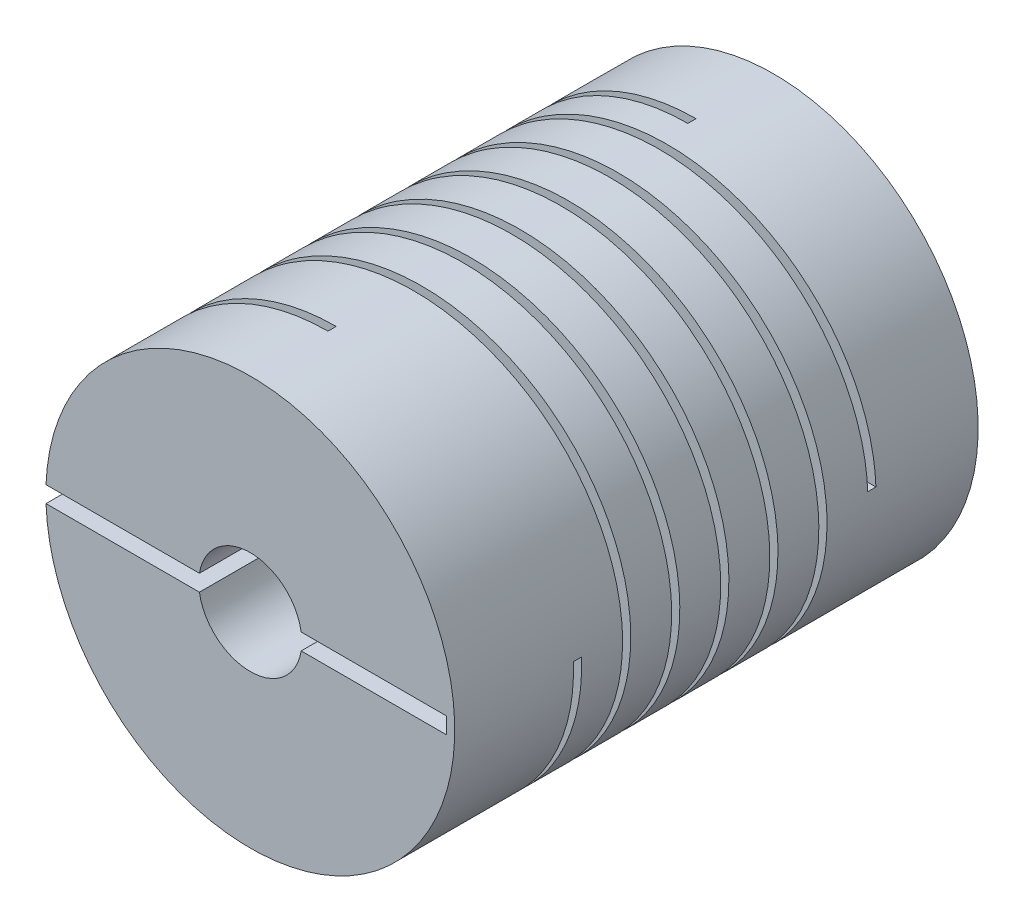
SolidWorks part; units mm, degrees
material "3,3523 (EN-AW 5052)"
ref_plane "Plano frontal" through (0, 0, 0) normal (0, 0, 1) x (1, 0, 0)
ref_plane "Plano superior" through (0, 0, 0) normal (0, 1, 0) x (1, 0, 0)
ref_plane "Plano direito" through (0, 0, 0) normal (1, 0, 0) x (0, 0, -1)
sketch "Esboço1" plane through (0, 0, 0) normal (0, 0, 1) x (1, 0, 0)
  circle A0 centre (0, 0) radius 12.5
  dimension "D1" = 25
extrude "Ressalto-extrusão1" add sketch "Esboço1" along normal blind 32
sketch "Esboço2" plane through (0, 0, 32) normal (0, 0, 1) x (1, 0, 0)
  circle A0 centre (0, 0) radius 3.15
  dimension "D1" = 6.3
extrude "Corte-extrusão1" cut sketch "Esboço2" against normal blind 32
sketch "Esboço3" plane through (0, 0, 0) normal (1, 0, 0) x (0, 0, -1)
  line L0 (-27, 12.5) -> (-27, -12.5) construction
  line L1 (-26.75, 12.5) -> (-26.75, -12.5)
  line L2 (-27.25, 12.5) -> (-27.25, -12.5)
  line L3 (-5, 12.5) -> (-5, -12.5) construction
  line L4 (-4.75, 12.5) -> (-4.75, -12.5)
  line L5 (-5.25, 12.5) -> (-5.25, -12.5)
  line L6 (-32, 12.5) -> (-32, -12.5) construction
  line L7 (0, -12.5) -> (0, 12.5) construction
  arc A0 (-26.75, 12.5) -> (-27.25, 12.5) centre (-27, 12.5) ccw
  arc A1 (-27.25, -12.5) -> (-26.75, -12.5) centre (-27, -12.5) ccw
  arc A2 (-4.75, 12.5) -> (-5.25, 12.5) centre (-5, 12.5) ccw
  arc A3 (-5.25, -12.5) -> (-4.75, -12.5) centre (-5, -12.5) ccw
  point P2 (-27, 0)
  point P7 (-5, 0)
  dimension "D5" = 0.25
  dimension "D6" = 0.25
  dimension "D1" = 5
  dimension "D2" = 5
  dimension "D3" = 25
  dimension "D4" = 25
extrude "Corte-extrusão2" cut sketch "Esboço3" against normal blind 16
ref_plane "Plano1" through (0, 0, 24.5) normal (0, 0, 1) x (1, 0, 0)
sketch "Esboço5" plane through (0, 0, 24.5) normal (0, 0, 1) x (1, 0, 0)
  circle A0 centre (0, 0) radius 12.5
  dimension "D1" = 25
curve "Hélice/Espiral1" pitch 3 height 18 radius 12.5 centre (0, 0, 24.5) axis (0, 0, -1) start towards (1, 0, 0)
sketch "Esboço6" plane through (0, 0, 0) normal (0, 1, 0) x (1, 0, 0)
  line L0 (12.5, -32) -> (12.5, 0) construction
  line L1 (12.5, -6.25) -> (2.5, -6.25)
  line L2 (12.5, -6.25) -> (12.5, -6.75)
  line L3 (12.5, -6.75) -> (2.5, -6.75)
  line L4 (2.5, -6.25) -> (2.5, -6.75)
  spline S0 degree 3 poles (12.5, -24.5) (12.5, -24.4379) (11.8491, -24.3123) (9.0689, -24.125) (4.9081, -23.9375) (0, -23.75) (-4.9081, -23.5625) (-9.0689, -23.375) (-11.8491, -23.1875) (-12.8254, -23) (-11.8491, -22.8125) (-9.0689, -22.625) (-4.9081, -22.4375) (0, -22.25) (4.9081, -22.0625) (9.0689, -21.875) (11.8491, -21.6875) (12.8254, -21.5) (11.8491, -21.3125) (9.0689, -21.125) (4.9081, -20.9375) (0, -20.75) (-4.9081, -20.5625) (-9.0689, -20.375) (-11.8491, -20.1875) (-12.8254, -20) (-11.8491, -19.8125) (-9.0689, -19.625) (-4.9081, -19.4375) (0, -19.25) (4.9081, -19.0625) (9.0689, -18.875) (11.8491, -18.6875) (12.8254, -18.5) (11.8491, -18.3125) (9.0689, -18.125) (4.9081, -17.9375) (0, -17.75) (-4.9081, -17.5625) (-9.0689, -17.375) (-11.8491, -17.1875) (-12.8254, -17) (-11.8491, -16.8125) (-9.0689, -16.625) (-4.9081, -16.4375) (0, -16.25) (4.9081, -16.0625) (9.0689, -15.875) (11.8491, -15.6875) (12.8254, -15.5) (11.8491, -15.3125) (9.0689, -15.125) (4.9081, -14.9375) (0, -14.75) (-4.9081, -14.5625) (-9.0689, -14.375) (-11.8491, -14.1875) (-12.8254, -14) (-11.8491, -13.8125) (-9.0689, -13.625) (-4.9081, -13.4375) (0, -13.25) (4.9081, -13.0625) (9.0689, -12.875) (11.8491, -12.6875) (12.8254, -12.5) (11.8491, -12.3125) (9.0689, -12.125) (4.9081, -11.9375) (0, -11.75) (-4.9081, -11.5625) (-9.0689, -11.375) (-11.8491, -11.1875) (-12.8254, -11) (-11.8491, -10.8125) (-9.0689, -10.625) (-4.9081, -10.4375) (0, -10.25) (4.9081, -10.0625) (9.0689, -9.875) (11.8491, -9.6875) (12.8254, -9.5) (11.8491, -9.3125) (9.0689, -9.125) (4.9081, -8.9375) (0, -8.75) (-4.9081, -8.5625) (-9.0689, -8.375) (-11.8491, -8.1875) (-12.8254, -8) (-11.8491, -7.8125) (-9.0689, -7.625) (-4.9081, -7.4375) (0, -7.25) (4.9081, -7.0625) (9.0689, -6.875) (11.8491, -6.6877) (12.5, -6.5621) (12.5, -6.5) knots 0 0 0 0 0.010417 0.020833 0.03125 0.041667 0.052083 0.0625 0.072917 0.083333 0.09375 0.104167 0.114583 0.125 0.135417 0.145833 0.15625 0.166667 0.177083 0.1875 0.197917 0.208333 0.21875 0.229167 0.239583 0.25 0.260417 0.270833 0.28125 0.291667 0.302083 0.3125 0.322917 0.333333 0.34375 0.354167 0.364583 0.375 0.385417 0.395833 0.40625 0.416667 0.427083 0.4375 0.447917 0.458333 0.46875 0.479167 0.489583 0.5 0.510417 0.520833 0.53125 0.541667 0.552083 0.5625 0.572917 0.583333 0.59375 0.604167 0.614583 0.625 0.635417 0.645833 0.65625 0.666667 0.677083 0.6875 0.697917 0.708333 0.71875 0.729167 0.739583 0.75 0.760417 0.770833 0.78125 0.791667 0.802083 0.8125 0.822917 0.833333 0.84375 0.854167 0.864583 0.875 0.885417 0.895833 0.90625 0.916667 0.927083 0.9375 0.947917 0.958333 0.96875 0.979167 0.989583 1 1 1 1 construction
  point P8 (12.5, -6.5)
  dimension "D1" = 0.5
  dimension "D2" = 10
  dimension "D3" = 0.25
sweep "Varredura de corte5" cut profiles "Esboço6" path "Hélice/Espiral1" align with end faces yes
sketch "Esboço7" plane through (0, 0, 0) normal (0, 1, 0) x (1, 0, 0)
  line L0 (12, 0) -> (8.5, -4.75)
  line L1 (12.5, 0) -> (-12.5, 0) construction
  line L2 (8.5, -4.75) -> (-12.5, -4.75)
  line L3 (-12.5, -4.75) -> (-12.5, 0)
  line L4 (-12.5, 0) -> (12, 0)
  dimension "D1" = 24.5
  dimension "D2" = 21
  dimension "D3" = 12.5
extrude "Corte-extrusão3" cut sketch "Esboço7" against normal mid plane 1
sketch "Esboço8" plane through (0, 0, 0) normal (0, 1, 0) x (1, 0, 0)
  line L0 (12, -32) -> (8.5, -27.25)
  line L1 (-12.5, -32) -> (12.5, -32) construction
  line L2 (8.5, -27.25) -> (-12.5, -27.25)
  line L3 (-12.5, -27.25) -> (-12.5, -32)
  line L4 (-12.5, -32) -> (12, -32)
  line L5 (0, -27.25) -> (-12.5, -27.25) construction
  dimension "D1" = 24.5
  dimension "D2" = 12.5
  dimension "D3" = 21
extrude "Corte-extrusão4" cut sketch "Esboço8" against normal mid plane 1
ref_plane "Plano2" through (0, -9.5, 0) normal (0, 1, 0) x (-1, 0, 0)
hole_wizard "Rebaixo para parafuso com cabeça panela de M1.61" positions "Esboço10" profile "Esboço9" counterbore size "M1.6" standard "ISO" end condition through all
sketch "Esboço10" plane through (0, -9.5, 0) normal (0, 1, 0) x (-1, 0, 0)
  point P0 (9.789, 2.3198)
  point P3 (9.789, 29.9398)
sketch "Esboço9" plane through (-9.789, -9.5, 2.3198) normal (1, 0, 0) x (0, 0, -1)
  line L0 (0, 0) -> (0, 22.6433)
  line L1 (0, 22.6433) -> (0.9, 22.6433)
  line L3 (0.9, 22.6433) -> (0.9, 3.5)
  line L4 (0.9, 3.5) -> (1.75, 3.5)
  line L5 (1.75, 3.5) -> (1.75, 0)
  line L7 (1.75, 0) -> (0, 0)
  line L11 (0, -6.35) -> (0, 107.95) construction
  dimension "Thru Hole Dia." = 1.8
  dimension "Thru Hole Depth" = 22.6433
  dimension "C'Bore Dia." = 3.5
  dimension "C'Bore Depth" = 3.5
